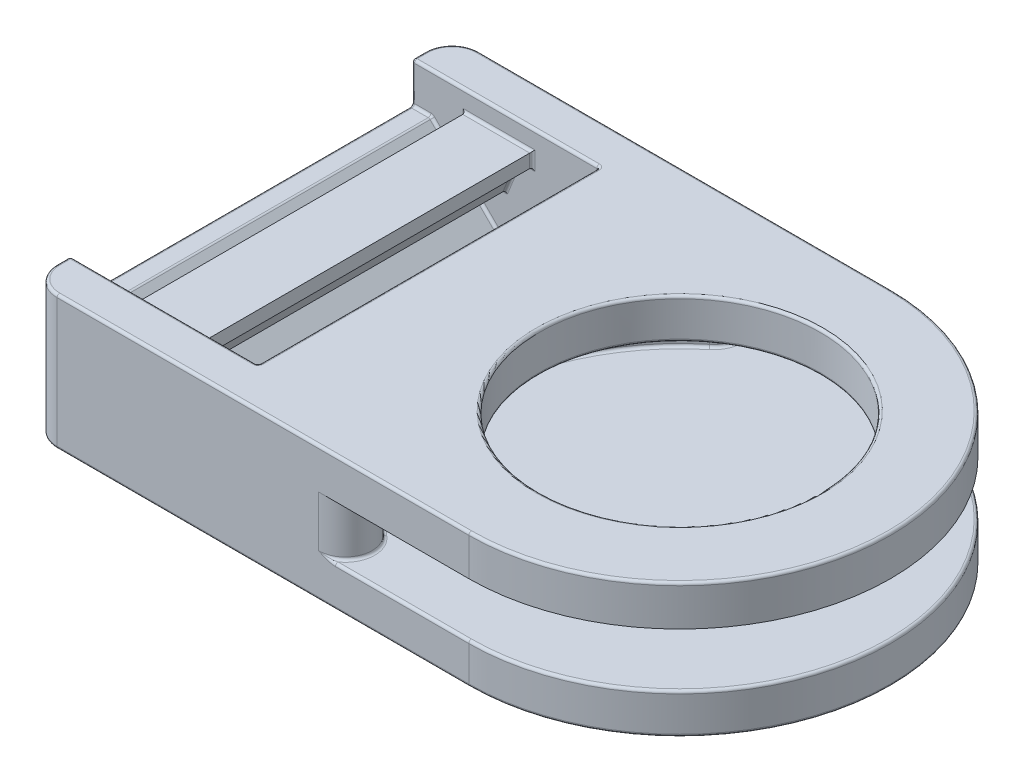
SolidWorks part; units mm, degrees
ref_plane "Спереди" through (0, 0, 0) normal (0, 0, 1) x (1, 0, 0)
ref_plane "Сверху" through (0, 0, 0) normal (0, 1, 0) x (1, 0, 0)
ref_plane "Справа" through (0, 0, 0) normal (1, 0, 0) x (0, 0, -1)
sketch "Эскиз1" plane through (0, 0, 0) normal (0, 1, 0) x (1, 0, 0)
  line L2 (-24.25, 13.75) -> (-24.25, -13.75)
  line L5 (-22.25, 15.75) -> (8.5, 15.75)
  line L6 (-22.25, -15.75) -> (8.5, -15.75)
  arc A0 (8.5, 15.75) -> (8.5, -15.75) centre (8.5, 0) cw
  arc A1 (-24.25, -13.75) -> (-22.25, -15.75) centre (-22.25, -13.75) ccw
  arc A2 (-22.25, 15.75) -> (-24.25, 13.75) centre (-22.25, 13.75) ccw
  dimension "D1" = 2
extrude "Бобышка-Вытянуть1" add sketch "Эскиз1" along normal blind 10
sketch "Эскиз2" plane through (0, 10, 0) normal (0, 1, 0) x (1, 0, 0)
  circle A0 centre (8.5, 0) radius 10.5
sketch "Эскиз7" plane through (0, 0, 0) normal (0, -1, 0) x (1, 0, 0)
  circle A0 centre (8.5, 0) radius 15.75
sketch "Эскиз8" plane through (0, 10, 0) normal (0, 1, 0) x (1, 0, 0)
  line L0 (-10.25, 12.75) -> (-10.25, -12.75)
  line L1 (-24.25, 13.75) -> (-24.25, -13.75) construction
  line L3 (-10.25, -12.75) -> (-24.25, -12.75)
  line L5 (-10.25, 12.75) -> (-24.25, 12.75)
  line L6 (-24.25, 12.75) -> (-24.25, -12.75)
extrude "Вырез-Вытянуть5" cut sketch "Эскиз8" against normal through all
sketch "Эскиз9" plane through (0, 0, -12.75) normal (0, 0, 1) x (1, 0, 0)
  line L0 (-18.25, 5) -> (-17.25, 5)
  line L2 (-15.25, 8.5) -> (-20.25, 8.5)
  line L3 (-20.25, 8.5) -> (-20.25, 7.5)
  line L4 (-17.25, 5) -> (-17.2445, 5.0056)
  line L5 (-15.25, 7.5) -> (-15.25, 8.5)
  line L7 (-24.25, 7) -> (-22.75, 7)
  line L8 (-20.25, 7.5) -> (-19.25, 7.5)
  line L9 (-19.25, 7.5) -> (-18.25, 5)
  line L11 (-15.25, 7.5) -> (-16.25, 7.5)
  line L12 (-16.25, 7.5) -> (-17.25, 5)
  line L16 (-17.25, 1.5) -> (-22.75, 7)
  line L18 (-24.25, 7) -> (-24.25, 5.5)
  line L19 (-24.25, 5.5) -> (-23.25, 5.5)
  line L20 (-23.25, 5.5) -> (-19.25, 1.5)
  line L21 (-19.25, 1.5) -> (-17.25, 1.5)
  line M1 (-10.25, 10) -> (-24.25, 10)
  line M2 (-24.25, 10) -> (-24.25, 0)
extrude "Бобышка-Вытянуть3" add sketch "Эскиз9" along normal blind 25.5 contours L20 L21 L16 L7 L19 M2 | L12 L11 L5 L3 L8 L9 L0 M1 region at (-17.75, 7.2292, -12.75) region at (-21.0907, 4.2912, -12.75)
fillet "Скругление3" radius 0.2 44 edges at (-24.25, 7, 0) (-24.25, 5.5, 0) (-17.25, 1.5, 0) (-22.75, 7, 0) (-23.25, 5.5, 0) (-19.25, 1.5, 0) (-23.75, 5.5, -12.75) (-21.25, 3.5, -12.75) (-18.25, 1.5, -12.75) (-20, 4.25, -12.75) (-23.5, 7, -12.75) (-24.25, 8.5, -12.75) (-20.25, 8, -12.75) (-19.75, 7.5, -12.75) (-18.75, 6.25, -12.75) (-17.75, 5, -12.75) (-16.75, 6.25, -12.75) (-15.75, 7.5, -12.75) (-15.25, 8, -12.75) (-10.25, 5, -12.75) (-24.25, 2.75, -12.75) (-15.25, 8, 12.75) (-15.75, 7.5, 12.75) (-16.75, 6.25, 12.75) (-17.75, 5, 12.75) (-18.75, 6.25, 12.75) (-19.75, 7.5, 12.75) (-20.25, 8, 12.75) (-24.25, 8.5, 12.75) (-23.5, 7, 12.75) (-20, 4.25, 12.75) (-18.25, 1.5, 12.75) (-21.25, 3.5, 12.75) (-23.75, 5.5, 12.75) (-24.25, 2.75, 12.75) (-10.25, 5, 12.75) (-17.75, 8.5, -12.75) (-17.75, 8.5, 12.75) (-10.25, 0, 0) (-10.25, 10, 0) (-17.25, 10, -12.75) (-17.25, 0, -12.75) (-17.25, 0, 12.75) (-17.25, 10, 12.75)
extrude "Вырез-Вытянуть6" cut sketch "Эскиз2" against normal blind 3
extrude "Вырез-Вытянуть7" cut sketch "Эскиз7" against normal blind 4 from offset 3 offset against normal yes
fillet "Скругление4" radius 2 2 edges at (8.5, 5, -15.75) (8.5, 5, 15.75)
fillet "Скругление5" radius 0.2 26 edges at (-24.1914, 0.0586, 12.8086) (-24.1914, 0.0586, -12.8086) (-24.1914, 9.9414, 12.8086) (-24.1914, 9.9414, -12.8086) (2.8875, 3, 15.75) (-0.841, 3, 14.4213) (-7.25, 3, 0) (-0.841, 3, -14.4213) (2.8875, 3, -15.75) (24.25, 3, 0) (-24.25, 0, 13.35) (-23.6642, 0, 15.1642) (-6.875, 0, 15.75) (24.25, 0, 0) (-6.875, 0, -15.75) (-23.6642, 0, -15.1642) (-24.25, 0, -13.35) (-23.6642, 10, -15.1642) (-6.875, 10, -15.75) (24.25, 10, 0) (-6.875, 10, 15.75) (-23.6642, 10, 15.1642) (-24.25, 10, 13.35) (-24.25, 10, -13.35) (8.5, 10, 10.5) (8.5, 7, -10.5)
